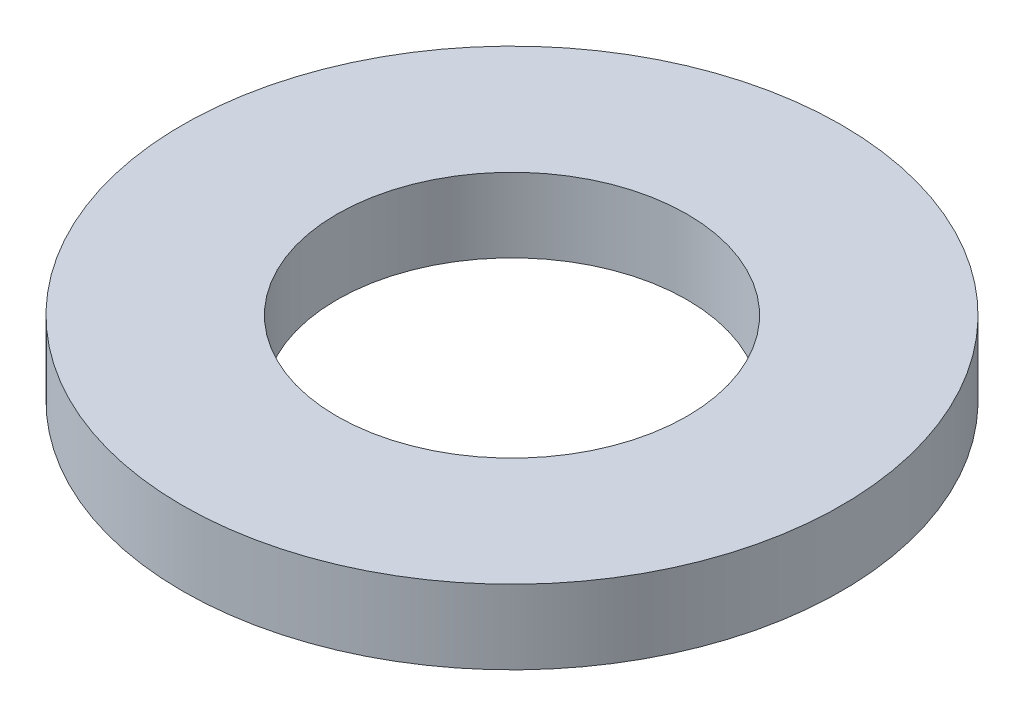
SolidWorks part; units mm, degrees
ref_plane "Front Plane" through (0, 0, 0) normal (0, 0, 1) x (1, 0, 0)
ref_plane "Top Plane" through (0, 0, 0) normal (0, 1, 0) x (1, 0, 0)
ref_plane "Right Plane" through (0, 0, 0) normal (1, 0, 0) x (0, 0, -1)
sketch "Sketch1" plane through (0, 0, 0) normal (0, 1, 0) x (1, 0, 0)
  circle A0 centre (0, 0) radius 80
  dimension "FLANGE_OD" = 160
extrude "Boss-Extrude1" add sketch "Sketch1" along normal blind 18
sketch "Sketch2" plane through (0, 0, 0) normal (0, 1, 0) x (1, 0, 0)
  circle A0 centre (0, 0) radius 42.5
  dimension "BORE_D" = 85
extrude "Cut-Extrude1" cut sketch "Sketch2" along normal through all
sketch "Sketch3" plane through (0, 18, 0) normal (0, 1, 0) x (1, 0, 0)
  circle A0 centre (0, 0) radius 33.2579 construction
  circle A1 centre (-33.2579, 0) radius 4.5405
  dimension "BOLT_D" = 9.081
  dimension "BOLT_PCD" = 66.5157
extrude "Cut-Extrude2" cut sketch "Sketch3" against normal blind 12.2541 rebuild error yes
pattern_circular "CirPattern1" count 5 over 360 rebuild error yes
